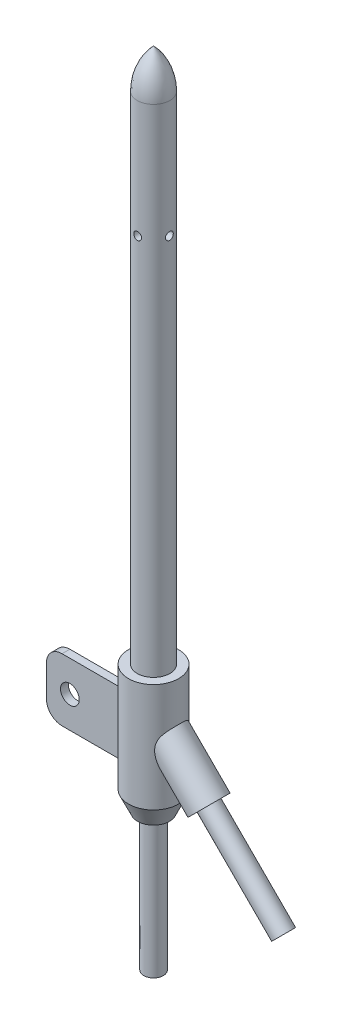
SolidWorks part; units mm, degrees
ref_plane "Front Plane" through (0, 0, 0) normal (0, 0, 1) x (1, 0, 0)
ref_plane "Top Plane" through (0, 0, 0) normal (0, 1, 0) x (1, 0, 0)
ref_plane "Right Plane" through (0, 0, 0) normal (1, 0, 0) x (0, 0, -1)
sketch "Sketch2" plane through (0, 0, 0) normal (0, 1, 0) x (1, 0, 0)
  circle A0 centre (0, 0) radius 2.085
  dimension "D1" = 4.17
extrude "Boss-Extrude1" add sketch "Sketch2" along normal blind 63.5
sketch "Sketch3" plane through (0, 0, 0) normal (0, 0, 1) x (1, 0, 0)
  line L0 (2.085, 63.5) -> (2.085, 60.967) construction
  line L1 (2.085, 0) -> (2.085, 63.5) construction
  line L2 (0, 63.5) -> (0, 68.5)
  line L3 (2.085, 63.5) -> (-2.085, 63.5) construction
  line L4 (2.085, 63.5) -> (0, 63.5)
  arc A0 (2.085, 63.5) -> (0, 68.5) centre (-4.9527, 63.5) ccw
  dimension "D1" = 5
revolve "Revolve2" add sketch "Sketch3" angle 360 about L2
sketch "Sketch4" plane through (0, 0, 0) normal (0, 0, 1) x (1, 0, 0)
  line L0 (0, 0) -> (0, -16.4)
  line L1 (0, -16.4) -> (2.05, -16.4)
  line L2 (2.05, -16.4) -> (3.21, -13.9)
  line L3 (3.21, -13.9) -> (3.21, 0)
  line L4 (3.21, 0) -> (0, 0)
  line L5 (0, 0) -> (0, -13.3708) construction
  dimension "D1" = 6.42
  dimension "D2" = 4.1
  dimension "D3" = 2.5
  dimension "D4" = 16.4
revolve "Revolve3" add sketch "Sketch4" angle 360 about L5
sketch "Sketch5" plane through (0, 0, 0) normal (0, 0, 1) x (1, 0, 0)
  line L0 (0, 0) -> (0, -16.4) construction
  line L1 (-2.05, -16.4) -> (2.05, -16.4) construction
  line L2 (0, -8.2) -> (3.21, -8.2) construction
  line L3 (3.21, -13.9) -> (3.21, 0) construction
  line L4 (0, -8.2) -> (-3.21, -8.2) construction
  line L5 (-3.21, 0) -> (-3.21, -13.9) construction
  point P13 (-3.21, -8.2)
  point P14 (3.21, -8.2)
ref_plane "Plane2" through (0, -8.2, 0) normal (0, 1, 0) x (1, 0, 0)
sketch "Sketch6" plane through (0, -8.2, 0) normal (0, 1, 0) x (1, 0, 0)
  line L0 (3.21, -6.2703) -> (3.21, 6.2703) construction
  point P2 (3.21, 0)
ref_plane "Plane3" through (5.705, -5.705, 0) normal (-0.7071, 0.7071, 0) x (0, 0, -1)
sketch "Sketch7" plane through (5.705, -5.705, 0) normal (-0.7071, 0.7071, 0) x (0, 0, -1)
  circle A0 centre (0, 3.5285) radius 2.2
  dimension "D1" = 4.4
extrude "Boss-Extrude2" add sketch "Sketch7" against normal blind 5.5 and the other way up to next
sketch "Sketch8" plane through (9.5941, -9.5941, 0) normal (0.7071, -0.7071, 0) x (0, 0, -1)
  circle A0 centre (0, -3.5285) radius 1.25
  circle A1 centre (0, -3.5285) radius 2.2 construction
  dimension "D1" = 2.5
extrude "Boss-Extrude3" add sketch "Sketch8" along normal blind 13.5
sketch "Sketch9" plane through (0, -16.4, 0) normal (0, -1, 0) x (1, 0, 0)
  circle A0 centre (0, 0) radius 1.25
  circle A1 centre (0, 0) radius 2.05 construction
  dimension "D1" = 2.5
extrude "Boss-Extrude4" add sketch "Sketch9" along normal blind 17.5
ref_plane "Plane4" through (-3.21, 0, 0) normal (1, 0, 0) x (0, 0, -1)
sketch "Sketch10" plane through (-3.21, 0, 0) normal (1, 0, 0) x (0, 0, -1)
  line L1 (0.5, -12.2) -> (-0.5, -12.2)
  line L2 (0.5, -12.2) -> (0.5, -4.2)
  line L3 (0.5, -4.2) -> (-0.5, -4.2)
  line L4 (-0.5, -12.2) -> (-0.5, -4.2)
  line L5 (0.5, -12.2) -> (-0.5, -4.2) construction
  line L6 (0.5, -4.2) -> (-0.5, -12.2) construction
  point P0 (0, -8.2)
  dimension "D1" = 8
  dimension "D2" = 1
extrude "Boss-Extrude5" add sketch "Sketch10" against normal blind 10 and the other way up to surface other way up to face at (0, 0, 3.21)
hole_wizard "M2 Clearance Hole1" positions "Sketch11" profile "Sketch12" hole size "M2" standard "ANSI Metric" end condition through all
sketch "Sketch11" plane through (0, 0, 0.5) normal (0, 0, 1) x (1, 0, 0)
  line L0 (-13.21, -8.2) -> (-10.21, -8.2) construction
  line L1 (-13.21, -4.2) -> (-13.21, -12.2) construction
  point P2 (-10.21, -8.2)
  dimension "D1" = 3
sketch "Sketch12" plane through (-10.21, -8.2, 0.5) normal (1, 0, 0) x (0, -1, 0)
  line L0 (0, 0) -> (0, 3.71)
  line L1 (0, 3.71) -> (1.2, 3.71)
  line L2 (1.2, 3.71) -> (1.2, 0)
  line L5 (1.2, 0) -> (0, 0)
  line L11 (0, -6.35) -> (0, 107.95) construction
  dimension "Thru Hole Dia." = 2.4
  dimension "Thru Hole Depth" = 3.71
fillet "Fillet1" radius 2 2 edges at (-13.21, -12.2, 0) (-13.21, -4.2, 0)
sketch "Sketch13" plane through (0, 0, 0) normal (0, 0, 1) x (1, 0, 0)
  circle A0 centre (0, 48.5) radius 0.5
  point P2 (0, 0)
  dimension "D2" = 1
  dimension "D1" = 20
extrude "Cut-Extrude1" cut sketch "Sketch13" against normal through all both and the other way through all
pattern_circular "CirPattern1" count 4 over 360 about axis through (0, 63.5, 0) along (0, -1, 0) of "Cut-Extrude1"
ref_plane "Plane5" through (0, 48.5, 0) normal (0, 1, 0) x (1, 0, 0)
ref_plane "Plane6" through (0, 38.5, 0) normal (0, 1, 0) x (1, 0, 0)
